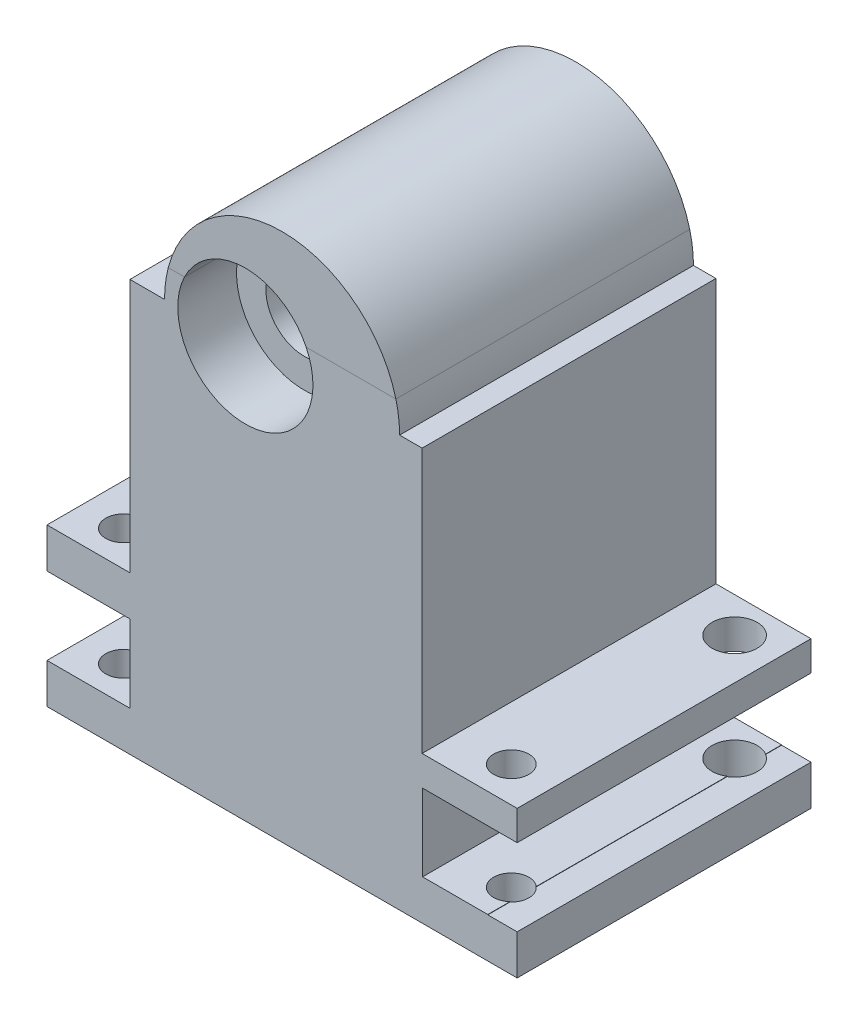
SolidWorks part; units mm, degrees
ref_plane "Plan de face" through (0, 0, 0) normal (0, 0, 1) x (1, 0, 0)
ref_plane "Plan de dessus" through (0, 0, 0) normal (0, 1, 0) x (1, 0, 0)
ref_plane "Plan de droite" through (0, 0, 0) normal (1, 0, 0) x (0, 0, -1)
sketch "Esquisse1" plane through (0, 0, 0) normal (0, 0, 1) x (1, 0, 0)
  line L0 (0, 0) -> (700, 0)
  line L1 (700, 0) -> (700, 450)
  line L2 (700, 450) -> (550, 450)
  line L3 (0, 0) -> (0, 450)
  line L4 (0, 450) -> (150, 450)
  arc A0 (550, 450) -> (150, 450) centre (350, 450) ccw
  dimension "D3" = 200
  dimension "D1" = 700
  dimension "D2" = 450
  dimension "D4" = 150
extrude "Boss.-Extru.1" add sketch "Esquisse1" along normal blind 500
sketch "Esquisse2" plane through (0, 0, 0) normal (0, -1, 0) x (1, 0, 0)
  line L0 (700, 500) -> (700, 0)
  line L1 (700, 0) -> (0, 0)
  line L2 (0, 0) -> (0, 500)
  line L3 (0, 500) -> (700, 500) construction
  line L4 (0, 500) -> (0, 0) construction
  line L5 (0, 500) -> (700, 500)
extrude "Boss.-Extru.2" add sketch "Esquisse2" along normal blind 250
sketch "Esquisse3" plane through (0, 0, 0) normal (0, 0, -1) x (-1, 0, 0)
  circle A0 centre (-287.5, 450) radius 65
extrude "Enlèv. mat.-Extru.1" cut sketch "Esquisse3" against normal blind 500
sketch "Esquisse4" plane through (0, 0, 0) normal (0, 0, -1) x (-1, 0, 0)
  line L0 (0, -50.3189) -> (-91.0727, -50.3189)
  line L1 (0, 450) -> (0, -250) construction
  line L2 (-91.0727, -50.3189) -> (-91.0727, -181.9886)
  line L3 (-91.0727, -181.9886) -> (0, -181.9886)
  line L4 (0, -181.9886) -> (0, -50.3189)
extrude "Enlèv. mat.-Extru.2" cut sketch "Esquisse4" against normal blind 500
sketch "Esquisse5" plane through (0, 0, 0) normal (0, 0, -1) x (-1, 0, 0)
  line L0 (-700, -181.4044) -> (-589.1123, -181.4044)
  line L1 (-700, -250) -> (-700, 450) construction
  line L2 (-589.1123, -181.4044) -> (-589.1123, -50.6587)
  line L3 (-589.1123, -50.6587) -> (-700, -50.6587)
  line L4 (-700, -50.6587) -> (-700, -181.4044)
extrude "Enlèv. mat.-Extru.3" cut sketch "Esquisse5" against normal blind 500
ref_plane "Plan1" through (0, 500, 0) normal (0, -1, 0) x (-1, 0, 0)
sketch "Esquisse6" plane through (0, 0, 500) normal (0, 0, 1) x (1, 0, 0)
  circle A0 centre (287.5, 450) radius 115
  circle A1 centre (287.5, 450) radius 65
extrude "Enlèv. mat.-Extru.4" cut sketch "Esquisse6" against normal blind 100
split "Fractionner2" trim tools "Plan1" bodies to split 108 resulting bodies 109 110
sketch "Esquisse7" plane through (0, 0, 0) normal (0, 0, -1) x (-1, 0, 0)
  circle A0 centre (-287.5, 450) radius 115
  circle A1 centre (-287.5, 450) radius 65
extrude "Enlèv. mat.-Extru.5" cut sketch "Esquisse7" against normal blind 100
sketch "Esquisse9" plane through (0, 0, 500) normal (0, 0, 1) x (1, 0, 0)
  line L1 (700, 450) -> (750, 450)
  line L2 (700, 450) -> (700, -50.6587)
  line L3 (700, -50.6587) -> (750, -50.6587)
  line L4 (750, 450) -> (750, -50.6587)
  line L5 (700, -250) -> (750, -250)
  line L6 (700, -250) -> (700, -181.9464)
  line L7 (700, -181.9464) -> (750, -181.9464)
  line L8 (750, -250) -> (750, -181.9464)
  line L9 (0, -50.3189) -> (-50, -50.3189)
  line L10 (0, -50.3189) -> (0, 450)
  line L11 (0, 450) -> (-50, 450)
  line L12 (-50, -50.3189) -> (-50, 450)
  line L13 (0, -181.9886) -> (-50, -181.9886)
  line L14 (0, -181.9886) -> (0, -250)
  line L15 (0, -250) -> (-50, -250)
  line L16 (-50, -181.9886) -> (-50, -250)
  dimension "D1" = 50
  dimension "D2" = 50
extrude "Boss.-Extru.3" add sketch "Esquisse9" against normal blind 500
sketch "Esquisse10" plane through (0, 0, 500) normal (0, 0, 1) x (1, 0, 0)
  line L0 (91.0727, -50.3189) -> (91.0727, 450)
  line L1 (150, 450) -> (-50, 450) construction
  line L2 (91.0727, 450) -> (-50, 450)
  line L3 (-50, 450) -> (-50, 17.6911)
  line L4 (-50, 450) -> (-50, -50.3189) construction
  line L5 (-50, 17.6911) -> (91.0727, 17.6911)
  line L8 (750, 0) -> (588.2822, 0)
  line L9 (750, -50.6587) -> (750, 450) construction
  line L10 (588.2822, 0) -> (588.2822, 450)
  line L11 (750, 450) -> (550, 450) construction
  line L12 (588.2822, 450) -> (750, 450)
  line L13 (750, 450) -> (750, 0)
  line M3 (150, 450) -> (-50, 450)
  line M4 (-50, 450) -> (-50, -50.3189)
  line M16 (750, -50.6587) -> (750, 450)
  line M17 (750, 450) -> (550, 450)
  dimension "D1" = 68.01
extrude "Enlèv. mat.-Extru.6" cut sketch "Esquisse10" against normal blind 500 contours L10 L8 M16 M17 | L5 L0 M4 M3 region at (20.5364, 233.8456, 500) region at (669.1411, 225, 500)
sketch "Esquisse11" plane through (0, 17.6911, 0) normal (0, 1, 0) x (1, 0, 0)
  line L0 (-50, 0) -> (91.0727, 0) construction
  line L1 (-50, 0) -> (-50, -500) construction
  line L2 (-50, -500) -> (91.0727, -500) construction
  circle A0 centre (20, -60) radius 30
  circle A1 centre (20, -440) radius 30
  dimension "D1" = 60
  dimension "D3" = 70
  dimension "D2" = 70
  dimension "D4" = 60
extrude "Enlèv. mat.-Extru.7" cut sketch "Esquisse11" against normal blind 310
sketch "Esquisse12" plane through (0, 0, 0) normal (0, 1, 0) x (1, 0, 0)
  line L0 (750, 0) -> (588.2822, 0) construction
  line L1 (750, 0) -> (750, -500) construction
  line L2 (750, -500) -> (588.2822, -500) construction
  circle A0 centre (680, -60) radius 38.3342
  circle A1 centre (680, -440) radius 30
  dimension "D3" = 60
  dimension "D1" = 60
  dimension "D2" = 70
extrude "Enlèv. mat.-Extru.8" cut sketch "Esquisse12" against normal blind 310
